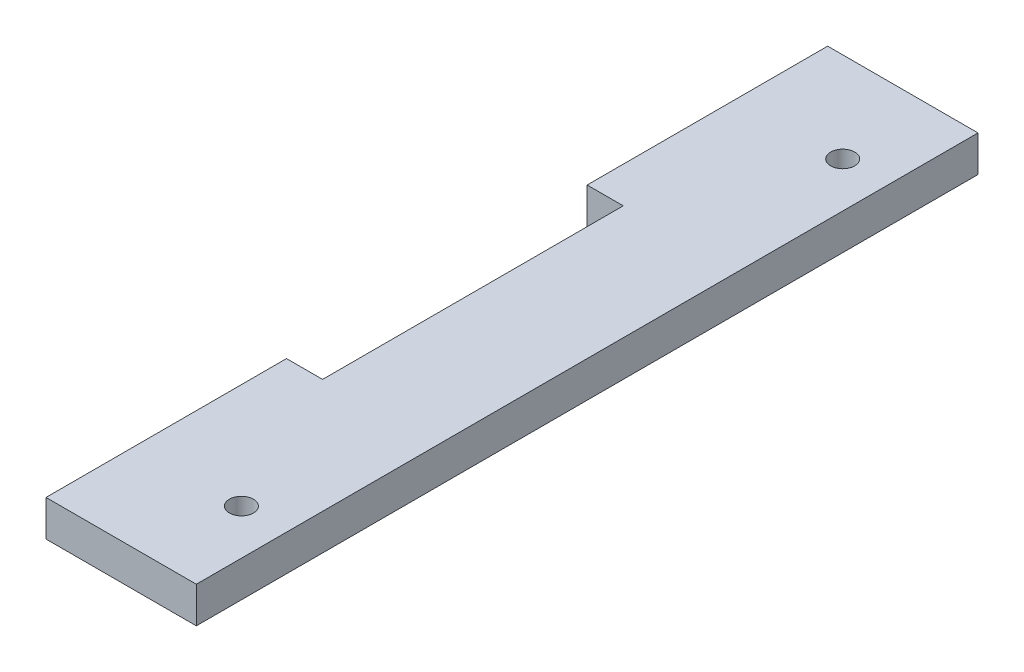
SolidWorks part; units mm, degrees
ref_plane "前视" through (0, 0, 0) normal (0, 0, 1) x (1, 0, 0)
ref_plane "上视" through (0, 0, 0) normal (0, 1, 0) x (1, 0, 0)
ref_plane "右视" through (0, 0, 0) normal (1, 0, 0) x (0, 0, -1)
sketch "Sketch1" plane through (0, 0, 0) normal (0, 1, 0) x (1, 0, 0)
  line L0 (-13.3162, 21.6054) -> (-7.3162, 21.6054)
  line L1 (-13.3162, 61.6054) -> (11.6838, 61.6054)
  line L2 (-13.3162, 61.6054) -> (-13.3162, -68.3946)
  line L3 (-13.3162, -68.3946) -> (11.6838, -68.3946)
  line L4 (11.6838, 61.6054) -> (11.6838, -68.3946)
  line L5 (-7.3162, 21.6054) -> (-7.3162, -28.3946)
  line L6 (-7.3162, -28.3946) -> (-13.3162, -28.3946)
  dimension "D1" = 130
  dimension "D2" = 25
  dimension "D3" = 6
  dimension "D4" = 40
  dimension "D5" = 40
extrude "Boss-Extrude1" add sketch "Sketch1" along normal blind 6 contours L5 L6 L2 L3 L4 L1 L0 region at (0.1499, 0, 3.3946)
sketch "Sketch2" plane through (0, 6, 0) normal (0, 1, 0) x (1, 0, 0)
  line L1 (-13.3162, 61.6054) -> (11.6838, 61.6054) construction
  line L2 (-13.3162, -68.3946) -> (11.6838, -68.3946) construction
  line L3 (11.6838, 61.6054) -> (11.6838, -68.3946) construction
  circle A0 centre (4.1838, -53.3946) radius 2
  circle A1 centre (4.1838, 46.6054) radius 2
  dimension "D1" = 4
  dimension "D3" = 4
  dimension "D2" = 7.5
  dimension "D4" = 15
  dimension "D5" = 15
  dimension "D6" = 7.5
extrude "Cut-Extrude1" cut sketch "Sketch2" against normal through all
